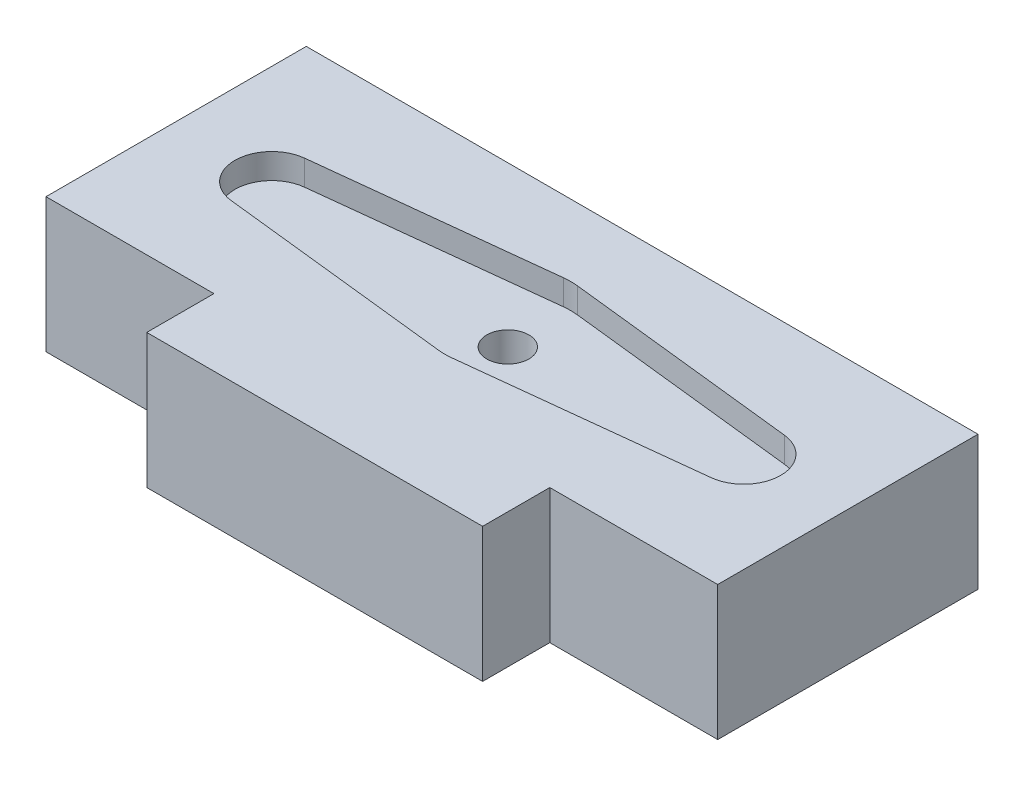
SolidWorks part; units mm, degrees
ref_plane "Front Plane" through (0, 0, 0) normal (0, 0, 1) x (1, 0, 0)
ref_plane "Top Plane" through (0, 0, 0) normal (0, 1, 0) x (1, 0, 0)
ref_plane "Right Plane" through (0, 0, 0) normal (1, 0, 0) x (0, 0, -1)
sketch "Sketch1" plane through (0, 0, 0) normal (0, 1, 0) x (1, 0, 0)
  circle A0 centre (0, 0) radius 32.5
  dimension "D1" = 65
extrude "Boss-Extrude1" add sketch "Sketch1" along normal blind 8
sketch "Sketch4" plane through (0, 8, 0) normal (0, 1, 0) x (1, 0, 0)
  line L0 (-14.2927, -2.1866) -> (-0.4137, -3.7271)
  line L1 (-14.2927, 2.1866) -> (-0.4137, 3.7271)
  line L2 (0, 0) -> (0, 4.5587) construction
  line L3 (14.2927, 2.1866) -> (0.4137, 3.7271)
  line L4 (14.2927, -2.1866) -> (0.4137, -3.7271)
  arc A0 (-0.4137, -3.7271) -> (0.4137, -3.7271) centre (0, 0) ccw
  arc A1 (-14.2927, 2.1866) -> (-14.2927, -2.1866) centre (-14.05, 0) ccw
  arc A2 (14.2927, 2.1866) -> (14.2927, -2.1866) centre (14.05, 0) cw
  arc A3 (0.4137, 3.7271) -> (-0.4137, 3.7271) centre (0, 0) ccw
  dimension "D1" = 7.5
  dimension "D2" = 4.4
  dimension "D3" = 14.05
extrude "Cut-Extrude1" cut sketch "Sketch4" against normal blind 1.5
sketch "Sketch5" plane through (0, 6.5, 0) normal (0, 1, 0) x (1, 0, 0)
  circle A0 centre (0, 0) radius 1.25
  dimension "D1" = 2.5
extrude "Cut-Extrude2" cut sketch "Sketch5" against normal through all both and the other way through all
sketch "Sketch6" plane through (0, 0, 0) normal (0, -1, 0) x (1, 0, 0)
  circle A0 centre (0, 0) radius 3.5
  dimension "D1" = 7
extrude "Cut-Extrude4" cut sketch "Sketch6" against normal blind 3.5
sketch "Sketch7" plane through (0, 8, 0) normal (0, 1, 0) x (1, 0, 0)
  line L1 (-59.8643, 36.9682) -> (64.0034, 36.9682)
  line L2 (-59.8643, 36.9682) -> (-59.8643, -45.9928)
  line L3 (-59.8643, -45.9928) -> (64.0034, -45.9928)
  line L4 (64.0034, 36.9682) -> (64.0034, -45.9928)
  line L5 (-22.3263, 11.8628) -> (21.0623, 11.8628)
  line L6 (-22.3263, 11.8628) -> (-22.3263, -9.7007)
  line L7 (-22.3263, -9.7007) -> (21.0623, -9.7007)
  line L8 (21.0623, 11.8628) -> (21.0623, -9.7007)
extrude "Boss-Extrude2" add sketch "Sketch7" against normal blind 8
sketch "Sketch9" plane through (0, 0, 0) normal (0, -1, 0) x (-1, 0, 0)
  line L1 (20, -11.5) -> (-20, -11.5)
  line L2 (20, -11.5) -> (20, 8)
  line L3 (20, 8) -> (-20, 8)
  line L4 (-20, -11.5) -> (-20, 8)
  line L5 (71.349, -60.8406) -> (-83.3169, -60.8406)
  line L6 (71.349, -60.8406) -> (71.349, 49.3126)
  line L7 (71.349, 49.3126) -> (-83.3169, 49.3126)
  line L8 (-83.3169, -60.8406) -> (-83.3169, 49.3126)
  dimension "D3" = 11.5
  dimension "D1" = 40
  dimension "D2" = 20
  dimension "D4" = 8
extrude "Cut-Extrude8" cut sketch "Sketch9" against normal through all both and the other way through all
sketch "Sketch10" plane through (0, 0, 0) normal (0, -1, 0) x (1, 0, 0)
  line L1 (-20, 11.5) -> (-10, 11.5)
  line L2 (-20, 11.5) -> (-20, 7.5)
  line L3 (-20, 7.5) -> (-10, 7.5)
  line L4 (-10, 11.5) -> (-10, 7.5)
  line L5 (20, 11.5) -> (10, 11.5)
  line L6 (20, 11.5) -> (20, 7.5)
  line L7 (20, 7.5) -> (10, 7.5)
  line L8 (10, 11.5) -> (10, 7.5)
  dimension "D1" = 4
  dimension "D2" = 10
  dimension "D3" = 4
  dimension "D4" = 10
extrude "Cut-Extrude10" cut sketch "Sketch10" against normal through all both and the other way through all
